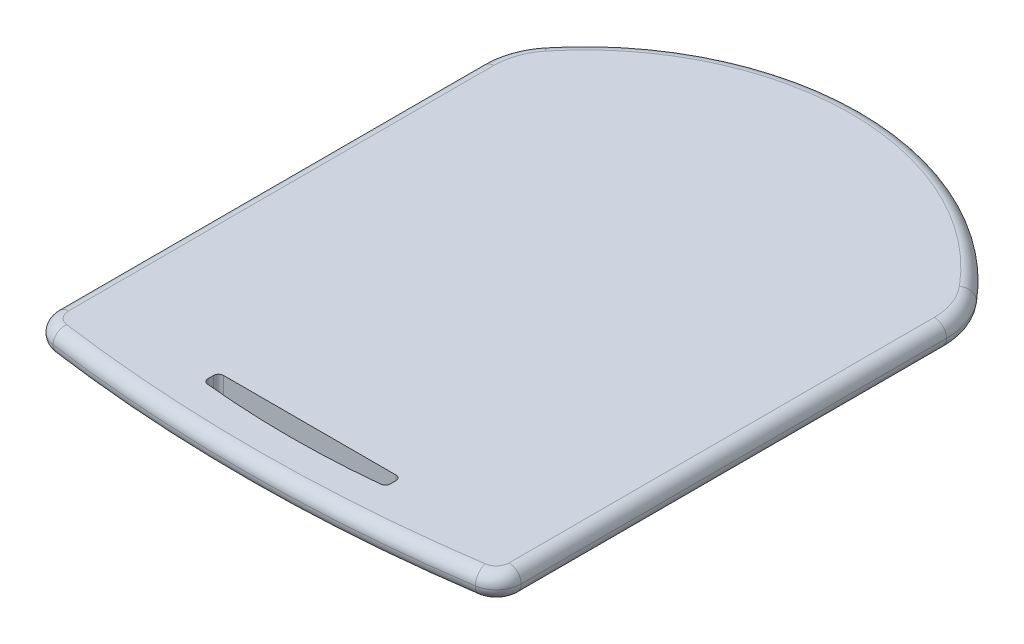
SolidWorks part; units mm, degrees
ref_plane "Front Plane" through (0, 0, 0) normal (0, 0, 1) x (1, 0, 0)
ref_plane "Top Plane" through (0, 0, 0) normal (0, 1, 0) x (1, 0, 0)
ref_plane "Right Plane" through (0, 0, 0) normal (1, 0, 0) x (0, 0, -1)
sketch "Sketch1" plane through (0, 0, 0) normal (0, 1, 0) x (1, 0, 0)
  line L0 (0, -80.8482) -> (0, 168.5463) construction
  line L5 (35.5, -58.8214) -> (-35.5, -58.8214)
  line L8 (-95.323, -62.0217) -> (95.0645, -62.0217) construction
  line L9 (0, 53.8013) -> (0.2356, 54.1543) construction
  line L11 (95.0645, -66.8932) -> (95.0645, 108.1068)
  line L20 (-95.323, -67.7796) -> (-95.3231, 107.2204)
  line L22 (-37.5, -63.222) -> (-37.5, -60.8214)
  line L23 (37.5, -63.222) -> (37.5, -60.8214)
  arc A1 (88.0423, 127.4726) -> (-88.563, 126.2681) centre (0.2356, 54.1543) ccw
  arc A2 (-86.4741, -77.9289) -> (86.3214, -77.0273) centre (-3.2318, 527.3314) ccw
  arc A3 (86.3214, -77.0273) -> (95.0645, -66.8932) centre (84.8197, -66.8932) ccw
  arc A4 (-95.323, -67.7796) -> (-86.4741, -77.9289) centre (-85.0783, -67.7796) ccw
  arc A5 (-95.3231, 107.2204) -> (-88.563, 126.2681) centre (-65.1083, 107.2204) cw
  arc A6 (95.0645, 108.1068) -> (88.0423, 127.4726) centre (64.8496, 108.1068) ccw
  arc A11 (-35.7051, -65.2115) -> (35.7051, -65.2115) centre (0, 281.1367) ccw
  arc A12 (35.5, -58.8214) -> (37.5, -60.8214) centre (35.5, -60.8214) cw
  arc A13 (-35.5, -58.8214) -> (-37.5, -60.8214) centre (-35.5, -60.8214) ccw
  arc A14 (-37.5, -63.222) -> (-35.7051, -65.2115) centre (-35.5, -63.222) ccw
  arc A15 (37.5, -63.222) -> (35.7051, -65.2115) centre (35.5, -63.222) cw
  point P0 (0, 0)
  point P23 (0, -58.8214)
  point P27 (-37.5, -62.0217)
  point P29 (37.5, -62.0217)
  dimension "D5" = 114.3923
extrude "Boss-Extrude1" add sketch "Sketch1" along normal blind 10
fillet "Fillet1" radius 5 16 edges at (92.5766, 10, 73.5854) (-0.0443, 10, 83.618) (-92.8002, 10, 74.5122) (-95.3231, 10, -19.7204) (-93.583, 10, -117.3262) (-0.5446, 10, -168.5439) (93.2547, 10, -118.4066) (92.5766, 0, 73.5854) (-0.0443, 0, 83.618) (-92.8002, 0, 74.5122) (-95.3231, 0, -19.7204) (-93.583, 0, -117.3262) (-0.5446, 0, -168.5439) (93.2547, 0, -118.4066) (95.0645, 10, -20.6068) (95.0645, 0, -20.6068)
